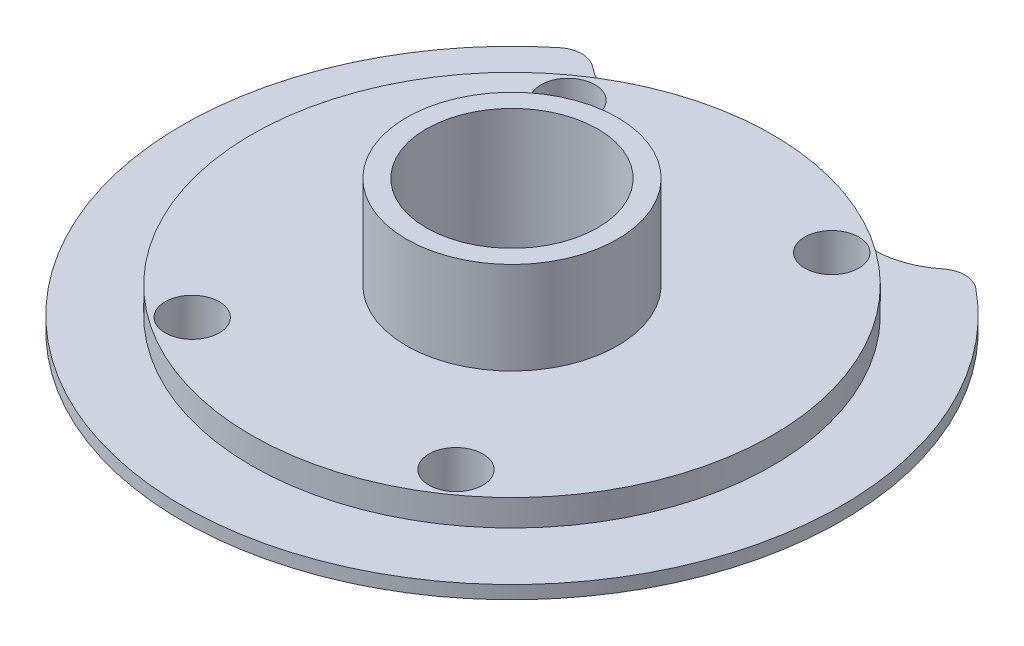
SolidWorks part; units mm, degrees
ref_plane "Front Plane" through (0, 0, 0) normal (0, 0, 1) x (1, 0, 0)
ref_plane "Top Plane" through (0, 0, 0) normal (0, 1, 0) x (1, 0, 0)
ref_plane "Right Plane" through (0, 0, 0) normal (1, 0, 0) x (0, 0, -1)
sketch "Sketch1" plane through (0, 0, 0) normal (0, 1, 0) x (1, 0, 0)
  circle A4 centre (0, 0) radius 12.5
  dimension "D1" = 25
extrude "Boss-Extrude1" add sketch "Sketch1" along normal blind 1.5
sketch "Sketch2" plane through (0, 0, 0) normal (0, -1, 0) x (1, 0, 0)
  circle A0 centre (0, 0) radius 3.25
  dimension "D1" = 6.5
extrude "Cut-Extrude1" cut sketch "Sketch2" against normal through all
sketch "Sketch3" plane through (0, 1.5, 0) normal (0, 1, 0) x (1, 0, 0)
  circle A0 centre (0, 0) radius 3.25 construction
  circle A1 centre (0, 0) radius 12.5
  circle A2 centre (0, 0) radius 12.5
  circle A3 centre (0, 0) radius 3.25
  circle A4 centre (0, 0) radius 4
  circle M4 centre (0, 0) radius 3.25
  dimension "D1" = 0
  dimension "D2" = 0.75
extrude "Boss-Extrude2" add sketch "Sketch3" along normal blind 3.5 contours A4 M4 region at (-3.8869, 1.5, 0)
sketch "Sketch4" plane through (0, 1.5, 0) normal (0, 1, 0) x (1, 0, 0)
  circle A0 centre (0, 0) radius 12.5 construction
  circle A1 centre (0, 0) radius 12.5
  circle A2 centre (0, 0) radius 9.875
  circle M4 centre (0, 0) radius 12.5
  dimension "D1" = 19.75
extrude "Cut-Extrude2" cut sketch "Sketch4" against normal blind 1 contours A2 M4 region at (-12.1464, 1.5, 0)
sketch "Sketch5" plane through (0, 0.5, 0) normal (0, 1, 0) x (1, 0, 0)
  line L0 (0, 0) -> (7.1697, 10.2394)
  line L1 (0, 0) -> (0, 12.5) construction
  line L2 (0, 0) -> (-7.1697, 10.2394)
  circle A0 centre (0, 0) radius 9.875 construction
  circle A1 centre (0, 0) radius 12.5
  circle A2 centre (0, 0) radius 12.5
  circle A3 centre (0, 0) radius 9.875
  circle M4 centre (0, 0) radius 9.875
  circle M5 centre (0, 0) radius 12.5
  dimension "D2" = 35
  dimension "D1" = 0
extrude "Cut-Extrude3" cut sketch "Sketch5" against normal through all contours L1 A3 L0 M5 | L1 A2 L2 M4 region at (3.3273, 0.5, -10.5528) region at (-3.3273, 0.5, -10.5528)
fillet "Fillet1" radius 3.125 2 edges at (-5.6641, 0.25, -8.0891) (5.6641, 0.25, -8.0891)
fillet "Fillet2" radius 1 2 edges at (-7.1697, 0.25, -10.2394) (7.1697, 0.25, -10.2394)
sketch "Sketch6" plane through (0, 0, 0) normal (0, -1, 0) x (1, 0, 0)
  line L0 (0, 0) -> (5, 0) construction
  line L1 (-5, -7.125) -> (5, -7.125) construction
  line L2 (-5, -7.125) -> (-5, 7.125) construction
  line L3 (-5, 7.125) -> (5, 7.125) construction
  line L4 (5, -7.125) -> (5, 7.125) construction
  line L5 (-5, -7.125) -> (5, 7.125) construction
  line L6 (-5, 7.125) -> (5, -7.125) construction
  line L7 (0, 0) -> (0, 7.125) construction
  circle A0 centre (5, 7.125) radius 1.025
  circle A1 centre (-5, 7.125) radius 1.025
  circle A2 centre (5, -7.125) radius 1.025
  circle A3 centre (-5, -7.125) radius 1.025
  point P0 (0, 0)
  dimension "D3" = 2.05
  dimension "D1" = 10
  dimension "D2" = 14.25
extrude "Cut-Extrude4" cut sketch "Sketch6" against normal through all contours A1 | A0 | A2 | A3 region at (5, 0, 7.125) region at (-5, 0, 7.125) region at (5, 0, -7.125) region at (-5, 0, -7.125)
